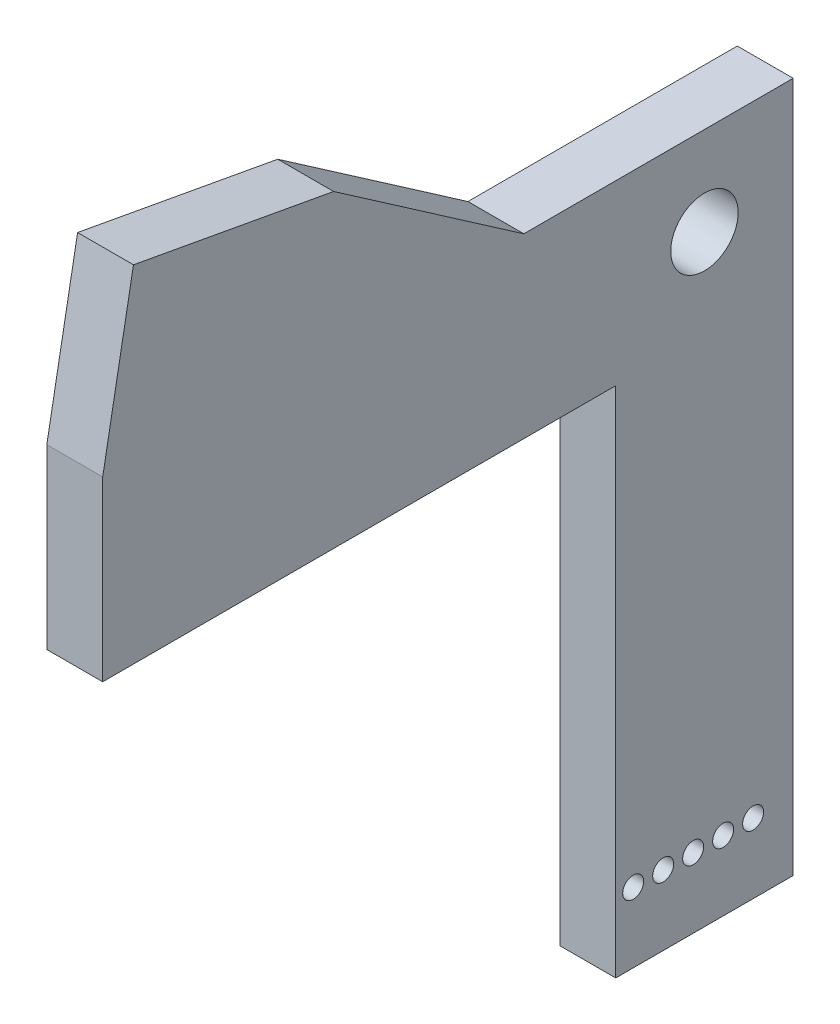
SolidWorks part; units mm, degrees
material "Hardboard"
ref_plane "Front Plane" through (0, 0, 0) normal (0, 0, 1) x (1, 0, 0)
ref_plane "Top Plane" through (0, 0, 0) normal (0, 1, 0) x (1, 0, 0)
ref_plane "Right Plane" through (0, 0, 0) normal (1, 0, 0) x (0, 0, -1)
sketch "Sketch1" plane through (0, 0, 0) normal (1, 0, 0) x (0, 0, -1)
  line L0 (-43.0661, 6.35) -> (6.35, 6.35)
  line L1 (6.35, 6.35) -> (6.35, -43.0661)
  line L2 (6.35, -43.0661) -> (-6.35, -43.0661)
  line L3 (-6.35, -43.0661) -> (-6.35, -6.35)
  line L4 (-6.35, -6.35) -> (-43.0661, -6.35)
  line L5 (-43.0661, -6.35) -> (-43.0661, 6.35)
  line L6 (-6.35, -6.35) -> (6.35, 6.35) construction
  line L7 (-43.0661, 6.35) -> (-40.8645, 18.3959)
  line L8 (-40.8645, 18.3959) -> (-26.5392, 15.7776)
  line L9 (-26.5392, 15.7776) -> (-12.928, 6.35)
  circle A0 centre (0, 0) radius 2.413
  circle A1 centre (-5.1, -38.0661) radius 0.75
  circle A2 centre (-2.9545, -38.0661) radius 0.75
  circle A3 centre (-0.8091, -38.0661) radius 0.75
  circle A4 centre (1.3364, -38.0661) radius 0.75
  circle A5 centre (3.4818, -38.0661) radius 0.75
  dimension "D1" = 4.826
  dimension "D2" = 1.5
  dimension "D3" = 1.25
  dimension "D4" = 5
  dimension "D5" = 5
extrude "Boss-Extrude1" add sketch "Sketch1" along normal mid plane 4 contours L9 L8 L7 L0 | L4 L6 A0 L0 L5 | L6 L3 L2 L1 A0 A5 A4 A3 A2 A1 region at (0, 11.0409, 31.1019) region at (0, 0.3051, 21.7283) region at (0, -21.4554, -0.3237)
